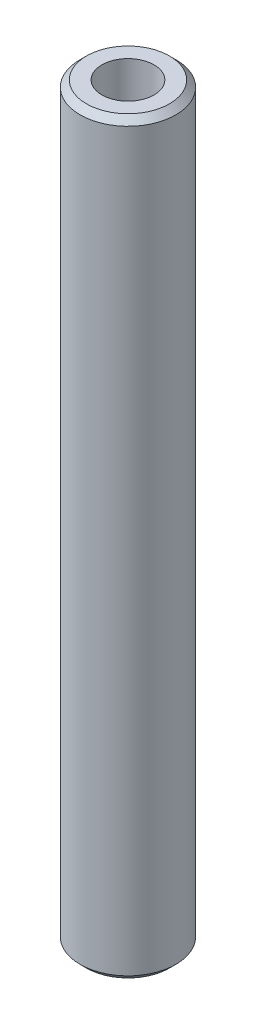
SolidWorks part; units mm, degrees
ref_plane "Front Plane" through (0, 0, 0) normal (0, 0, 1) x (1, 0, 0)
ref_plane "Top Plane" through (0, 0, 0) normal (0, 1, 0) x (1, 0, 0)
ref_plane "Right Plane" through (0, 0, 0) normal (1, 0, 0) x (0, 0, -1)
sketch "Sketch1" plane through (0, 0, 0) normal (0, 1, 0) x (1, 0, 0)
  circle A0 centre (0, 0) radius 15
  dimension "SHAFT_OD" = 30
extrude "Boss-Extrude1" add sketch "Sketch1" along normal blind 234.5363
sketch "Sketch2" plane through (0, 0, 0) normal (0, 1, 0) x (1, 0, 0)
  circle A0 centre (0, 0) radius 8.1807
  dimension "BORE_D" = 16.3613
extrude "Cut-Extrude1" cut sketch "Sketch2" along normal through all
chamfer "Chamfer1" distance 1.9944 angle 45 2 edges at (0, 234.5363, 15) (0, 0, 15)
